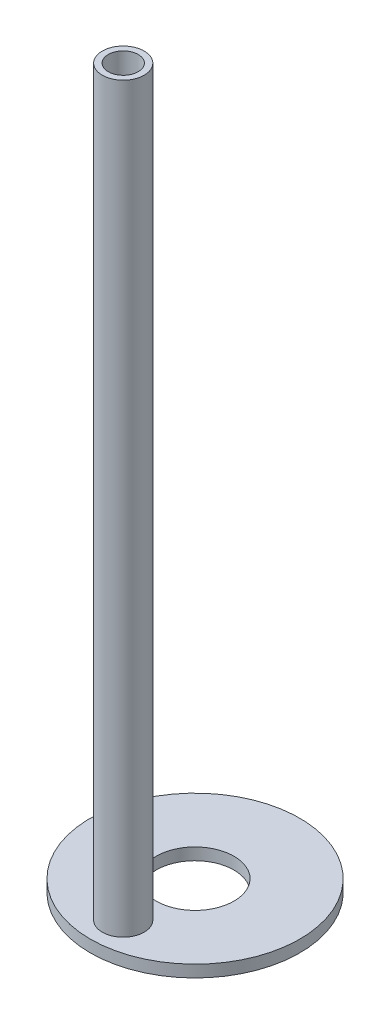
SolidWorks part; units mm, degrees
ref_plane "Front Plane" through (0, 0, 0) normal (0, 0, 1) x (1, 0, 0)
ref_plane "Top Plane" through (0, 0, 0) normal (0, 1, 0) x (1, 0, 0)
ref_plane "Right Plane" through (0, 0, 0) normal (1, 0, 0) x (0, 0, -1)
sketch "Sketch2" plane through (0, 0, 0) normal (0, 1, 0) x (1, 0, 0)
  line L0 (0, 1) -> (0, -1) construction
  line L1 (0, 0) -> (0, -12) construction
  circle A0 centre (0, 0) radius 17.5
  circle A2 centre (0, 0) radius 6.5
  circle A3 centre (0, -12) radius 3.5
  point P8 (0, 0)
  dimension "D1" = 35
  dimension "D2" = 13
  dimension "D3" = 12
  dimension "D6" = 7
  dimension "D4" = 2
extrude "Plate" add sketch "Sketch2" along normal mid plane 2 contours A0 A3 | A3 region at (-17.005, 0, 0) region at (0, 0, 12)
extrude "Rod" add sketch "Sketch2<4>" along normal blind 125 contours A3
sketch "Sketch2<4>" plane through (0, 0, 0) normal (0, 1, 0) x (1, 0, 0) same geometry as "Sketch2"
sketch "Sketch3" plane through (0, 125, 0) normal (0, 1, 0) x (1, 0, 0)
  circle A0 centre (0, -12) radius 2.5
  dimension "D1" = 5
extrude "Cut-Extrude1" cut sketch "Sketch3" against normal through all
